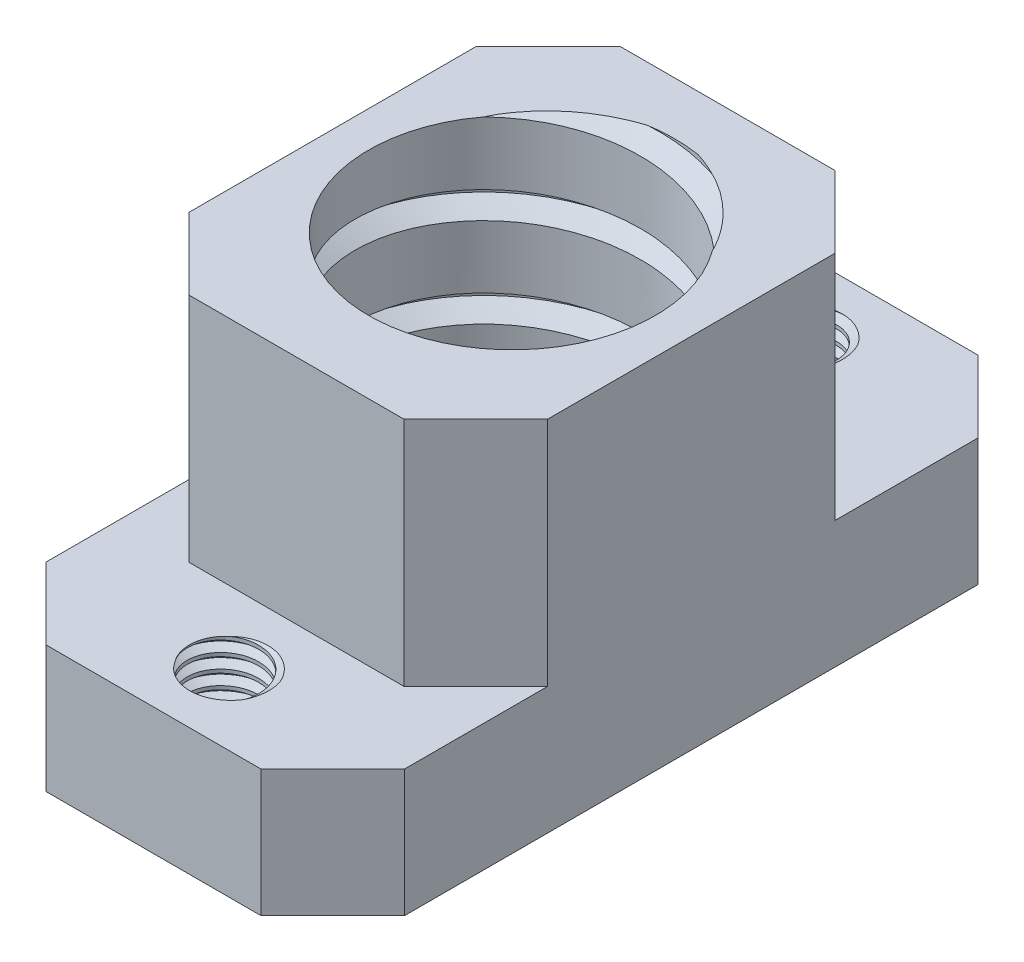
SolidWorks part; units mm, degrees
ref_plane "Front Plane" through (0, 0, 0) normal (0, 0, 1) x (1, 0, 0)
ref_plane "Top Plane" through (0, 0, 0) normal (0, 1, 0) x (1, 0, 0)
ref_plane "Right Plane" through (0, 0, 0) normal (1, 0, 0) x (0, 0, -1)
sketch "Sketch1" plane through (0, 0, 0) normal (0, 1, 0) x (1, 0, 0)
  line L1 (-4.0929, -16.6443) -> (5.9071, -16.6443)
  line L2 (-4.0929, -16.6443) -> (-4.0929, 3.3557)
  line L3 (-4.0929, 3.3557) -> (5.9071, 3.3557)
  line L4 (5.9071, -16.6443) -> (5.9071, 3.3557)
  circle A0 centre (0.9071, -6.6443) radius 4
  dimension "D3" = 8
  dimension "D1" = 10
  dimension "D2" = 20
extrude "Boss-Extrude1" add sketch "Sketch1" along normal blind 10
chamfer "Chamfer1" distance 2 angle 45 4 edges at (-4.0929, 5, -3.3557) (5.9071, 5, -3.3557) (5.9071, 5, 16.6443) (-4.0929, 5, 16.6443)
sketch "Sketch2" plane through (5.9071, 0, 0) normal (1, 0, 0) x (0, 0, -1)
  line L0 (-14.6443, 10) -> (1.3557, 10) construction
  line L1 (-0.6339, 10) -> (4.4268, 10)
  line L2 (-0.6339, 10) -> (-0.6339, 3.5436)
  line L3 (-0.6339, 3.5436) -> (4.4268, 3.5436)
  line L4 (4.4268, 10) -> (4.4268, 3.5436)
extrude "Cut-Extrude1" cut sketch "Sketch2" against normal blind 10 contours L3 L4 L1 L2
chamfer "Chamfer2" distance 2 angle 45 2 edges at (5.9071, 6.7718, 0.6339) (-4.0929, 6.7718, 0.6339)
sketch "Sketch3" plane through (0, 10, 0) normal (0, 1, 0) x (1, 0, 0)
  line L0 (4.9071, -6.6443) -> (0.9071, -6.6443) construction
  circle A0 centre (0.9071, -6.6443) radius 4 construction
sketch "Sketch4" plane through (0, 10, 0) normal (0, 1, 0) x (1, 0, 0)
  line L0 (5.9071, -8.6391) -> (-4.7831, -8.6391) construction
  line L1 (5.9071, -14.6443) -> (5.9071, -2.6339) construction
ref_plane "Plane1" through (0, 0, 6.6443) normal (0, 0, 1) x (1, 0, 0)
mirror "Mirror1" about plane through (0, 0, 6.6443) normal (0, 0, 1) of "Cut-Extrude1", "Chamfer2"
thread "Thread1" pitch 1 method cut profile "Thread Profile1" start angle 0, offset 1, length 0, pitch 2.5, diameter 8
ref_plane "Plane2" through (4.9071, -1, 6.6443) normal (0, 0, 1) x (1, 0, 0)
sketch "Thread Profile1" plane through (4.9071, -1, 6.6443) normal (0, 0, 1) x (1, 0, 0)
  line L0 (0, 0) -> (0, 1) construction
  line L1 (0, 0) -> (0.5413, 0.3125)
  line L2 (0.5413, 0.3125) -> (0.5413, 0.4375)
  line L3 (0.5413, 0.4375) -> (0, 0.75)
  line L4 (0.5413, 0.375) -> (0, 0.375) construction
  line L11 (0, 0) -> (0, 0.75)
  point P2 (0, 0)
  dimension "Pitch" = 1
  dimension "Profile_Angle" = 60
  dimension "Profile_Land" = 0.125
  dimension "Profile_Height" = 0.5413
sketch "Sketch10" plane through (0, 3.5436, 0) normal (0, 1, 0) x (1, 0, 0)
  circle A0 centre (0.9071, -14.6443) radius 1
  dimension "D1" = 2
  dimension "D2" = 8
extrude "Cut-Extrude2" cut sketch "Sketch10" against normal up to surface (3.5436 mm away) up to face at (0.9071, 0, 6.6443)
thread "Thread2" pitch 0.4 method cut profile "Thread Profile2" start angle 0, offset 1, length 0, pitch 0.4, diameter 2
ref_plane "Plane3" through (1.9071, -1, 14.6443) normal (0, 0, 1) x (1, 0, 0)
sketch "Thread Profile2" plane through (1.9071, -1, 14.6443) normal (0, 0, 1) x (1, 0, 0)
  line L0 (0, 0) -> (0, 0.4) construction
  line L1 (0, 0) -> (0.2165, 0.125)
  line L2 (0.2165, 0.125) -> (0.2165, 0.175)
  line L3 (0.2165, 0.175) -> (0, 0.3)
  line L4 (0.2165, 0.15) -> (0, 0.15) construction
  line L11 (0, 0) -> (0, 0.3)
  point P2 (0, 0)
  dimension "Pitch" = 0.4
  dimension "Profile_Angle" = 60
  dimension "Profile_Land" = 0.05
  dimension "Profile_Height" = 0.2165
mirror "Mirror2" about plane through (0, 0, 6.6443) normal (0, 0, 1) of "Cut-Extrude2", "Thread2"
